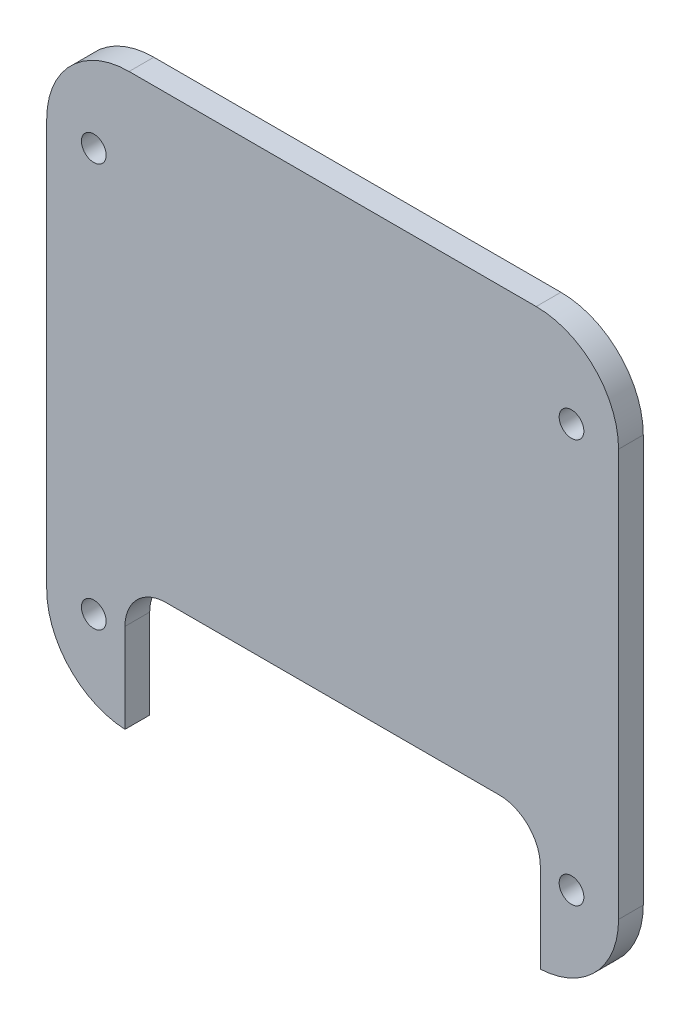
SolidWorks part; units mm, degrees
ref_plane "Front Plane" through (0, 0, 0) normal (0, 0, 1) x (1, 0, 0)
ref_plane "Top Plane" through (0, 0, 0) normal (0, 1, 0) x (1, 0, 0)
ref_plane "Right Plane" through (0, 0, 0) normal (1, 0, 0) x (0, 0, -1)
sketch "Sketch1" plane through (0, 0, 0) normal (0, 0, 1) x (1, 0, 0)
  line L1 (-34.7154, -34.7154) -> (34.7154, -34.7154)
  line L2 (-34.7154, -34.7154) -> (-34.7154, 34.7154)
  line L3 (-34.7154, 34.7154) -> (34.7154, 34.7154)
  line L4 (34.7154, -34.7154) -> (34.7154, 34.7154)
  line L5 (-34.7154, -34.7154) -> (34.7154, 34.7154) construction
  line L6 (-34.7154, 34.7154) -> (34.7154, -34.7154) construction
  point P0 (0, 0)
extrude "Boss-Extrude2" add sketch "Sketch1" along normal blind 3
sketch "Sketch6" plane through (0, 0, 3) normal (0, 0, 1) x (1, 0, 0)
  line L0 (29, 24.5) -> (29, 34.7154) construction
  line L1 (29, 24.5) -> (-29, 24.5) construction
  line L2 (29, -24.5) -> (-29, -24.5) construction
  line L4 (-29, -24.5) -> (-29, 24.5) construction
  line L5 (-25.2154, -34.7154) -> (-25.2154, -18.8892)
  line L69 (34.7154, 34.7154) -> (-34.7154, 34.7154) construction
  line L70 (29, -24.5) -> (29, -34.7154) construction
  line L71 (-34.7154, -34.7154) -> (34.7154, -34.7154) construction
  line L72 (-29, 24.5) -> (-34.7154, 24.5) construction
  line L73 (-34.7154, 34.7154) -> (-34.7154, -34.7154) construction
  line L74 (29, 24.5) -> (34.7154, 24.5) construction
  line L75 (34.7154, -34.7154) -> (34.7154, 34.7154) construction
  line L76 (-25.2154, -18.8892) -> (25.2154, -18.8892)
  line L77 (25.2154, -18.8892) -> (25.2154, -34.7154)
  line L78 (-25.2154, -34.7154) -> (25.2154, -34.7154)
  line L79 (-34.7154, -34.7154) -> (-25.2154, -34.7154) construction
  line L80 (25.2154, -34.7154) -> (34.7154, -34.7154) construction
  circle A16 centre (-29, 24.5) radius 1.5
  circle A17 centre (-29, -24.5) radius 1.5
  circle A18 centre (29, -24.5) radius 1.5
  circle A19 centre (29, 24.5) radius 1.5
  dimension "D1" = 58
  dimension "D3" = 9.5
  dimension "D2" = 49
  dimension "D4" = 15.8262
  dimension "D5" = 3
extrude "Cut-Extrude1" cut sketch "Sketch6" against normal blind 10
fillet "Fillet1" radius 10 1 edges at (34.7154, 34.7154, 1.5)
fillet "Fillet2" radius 10 3 edges at (34.7154, -34.7154, 1.5) (-34.7154, -34.7154, 1.5) (-34.7154, 34.7154, 1.5)
fillet "Fillet3" radius 4.9946 2 edges at (25.2154, -18.8892, 1.5) (-25.2154, -18.8892, 1.5)
